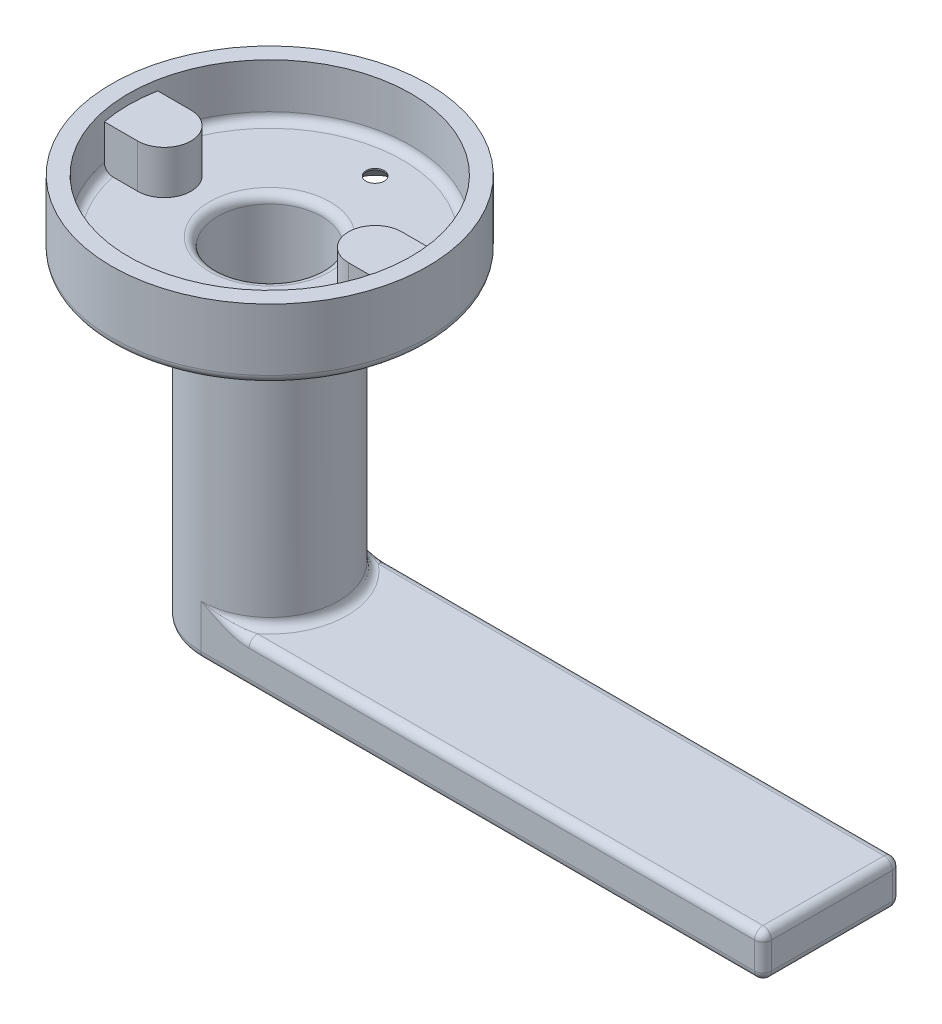
SolidWorks part; units mm, degrees
material "Custom Plastic"
ref_plane "Front Plane" through (0, 0, 0) normal (0, 0, 1) x (1, 0, 0)
ref_plane "Top Plane" through (0, 0, 0) normal (0, 1, 0) x (1, 0, 0)
ref_plane "Right Plane" through (0, 0, 0) normal (1, 0, 0) x (0, 0, -1)
sketch "Sketch1" plane through (0, 0, 0) normal (0, 0, 1) x (1, 0, 0)
  line L0 (-5.8443, 25.9927) -> (-2.7963, 25.9927)
  line L1 (-2.7963, 25.9927) -> (-2.7963, 14.8167)
  line L2 (-4.3203, 13.2927) -> (-17.4013, 13.2927)
  line L3 (-18.9253, 11.7687) -> (-18.9253, -35.9833)
  line L4 (-18.9253, -35.9833) -> (-21.9733, -35.9833)
  line L5 (-21.9733, -35.9833) -> (-21.9733, 5.842)
  line L6 (-21.9733, 5.842) -> (-21.9733, 14.8167)
  line L7 (-20.4493, 16.3407) -> (-7.3683, 16.3407)
  line L8 (-5.8443, 17.8647) -> (-5.8443, 25.9927)
  line L9 (-31.3713, -35.9833) -> (-31.3713, 32.3883) construction
  arc A0 (-17.4013, 13.2927) -> (-18.9253, 11.7687) centre (-17.4013, 11.7687) ccw
  arc A1 (-21.9733, 14.8167) -> (-20.4493, 16.3407) centre (-20.4493, 14.8167) cw
  arc A2 (-7.3683, 16.3407) -> (-5.8443, 17.8647) centre (-7.3683, 17.8647) ccw
  arc A3 (-2.7963, 14.8167) -> (-4.3203, 13.2927) centre (-4.3203, 14.8167) cw
  dimension "D8" = 1.524
  dimension "D1" = 3.048
  dimension "D2" = 3.048
  dimension "D3" = 3.048
  dimension "D4" = 12.7
  dimension "D5" = 61.976
  dimension "D6" = 12.446
  dimension "D7" = 28.575
revolve "Revolve1" add sketch "Sketch1" angle 360 about L9
sketch "Sketch2" plane through (0, 25.9927, 0) normal (0, 1, 0) x (1, 0, 0)
  line L0 (-12.3213, -4.826) -> (-6.3047, -4.826)
  line L1 (-12.3213, 4.826) -> (-6.3047, 4.826)
  line L2 (-50.4213, 4.826) -> (-56.438, 4.826)
  line L3 (-50.4213, -4.826) -> (-56.438, -4.826)
  circle A0 centre (-31.3713, 0) radius 19.05 construction
  arc A1 (-12.3213, 4.826) -> (-12.3213, -4.826) centre (-12.3213, 0) ccw
  circle A5 centre (-31.3713, 0) radius 25.527 construction
  arc A6 (-6.3047, -4.826) -> (-6.3047, 4.826) centre (-31.3713, 0) ccw
  circle A7 centre (-31.3713, 19.05) radius 1.651
  arc A8 (-50.4213, -4.826) -> (-50.4213, 4.826) centre (-50.4213, 0) ccw
  arc A9 (-56.438, 4.826) -> (-56.438, -4.826) centre (-31.3713, 0) ccw
  circle A10 centre (-31.3713, -19.05) radius 1.651
  point P21 (-31.3713, 0)
  point P25 (-31.3713, 0)
  dimension "D1" = 38.1
  dimension "D2" = 9.652
  dimension "D4" = 3.302
  dimension "D5" = 2
  dimension "D6" = 2
sketch "Sketch3" plane through (0, -35.9833, 0) normal (0, -1, 0) x (1, 0, 0)
  line L1 (-31.3713, -12.446) -> (68.7047, -12.446)
  line L2 (-31.3713, 12.446) -> (68.7047, 12.446)
  line L3 (70.2287, -10.922) -> (70.2287, 10.922)
  arc A0 (-31.3713, 12.446) -> (-31.3713, -12.446) centre (-31.3713, 0) ccw
  arc A1 (68.7047, 12.446) -> (70.2287, 10.922) centre (68.7047, 10.922) cw
  arc A2 (68.7047, -12.446) -> (70.2287, -10.922) centre (68.7047, -10.922) ccw
  point P6 (70.2287, 12.446)
  point P11 (70.2287, -12.446)
  dimension "D3" = 1.524
  dimension "D1" = 101.6
  dimension "D2" = 24.892
extrude "Boss-Extrude2" add sketch "Sketch3" along normal blind 7.874
fillet "Fillet1" radius 1.524 1 edges at (-31.3713, -35.9833, -9.398)
fillet "Fillet2" radius 1.524 1 edges at (-18.9253, -35.9833, 0)
extrude "Boss-Extrude3" add sketch "Sketch2" along normal blind 7.874 from surface contours A8 L2 A9 L3 | A1 L0 A6 L1 starting at face at (-31.3713, 16.3407, -10.922)
extrude "Cut-Extrude1" cut sketch "Sketch2<4>" against normal blind 31.496 contours A7 | A10
sketch "Sketch2<4>" plane through (0, 25.9927, 0) normal (0, 1, 0) x (1, 0, 0) same geometry as "Sketch2"
chamfer "Chamfer1" distance 2.794 angle 45 2 edges at (-31.3713, 13.2927, -20.701) (-31.3713, 13.2927, 17.399)
fillet "Fillet3" radius 1.524 13 edges at (69.7823, -43.8573, 11.9996) (70.2287, -43.8573, 0) (69.7823, -43.8573, -11.9996) (18.6667, -43.8573, -12.446) (-43.8173, -43.8573, 0) (-28.0744, -35.5196, -12.446) (21.8391, -35.9833, -12.446) (69.7823, -35.9833, -11.9996) (70.2287, -35.9833, 0) (69.7823, -35.9833, 11.9996) (18.6667, -43.8573, 12.446) (-28.0744, -35.5196, 12.446) (21.8391, -35.9833, 12.446)
